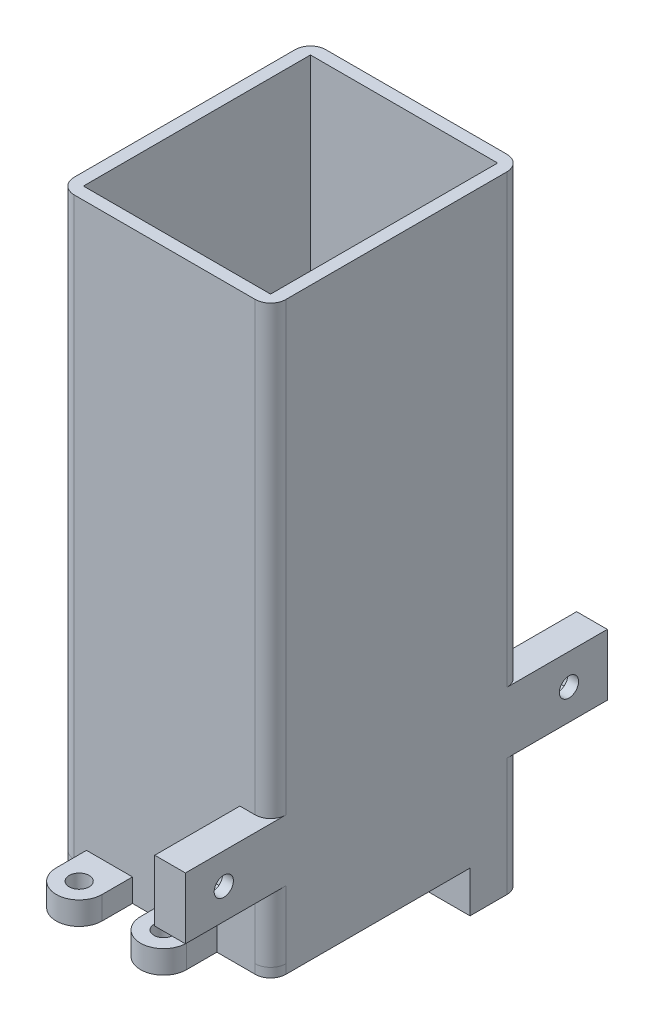
SolidWorks part; units mm, degrees
ref_plane "Front Plane" through (0, 0, 0) normal (0, 0, 1) x (1, 0, 0)
ref_plane "Top Plane" through (0, 0, 0) normal (0, 1, 0) x (1, 0, 0)
ref_plane "Right Plane" through (0, 0, 0) normal (1, 0, 0) x (0, 0, -1)
sketch "Sketch2" plane through (0, 0, 0) normal (0, 1, 0) x (1, 0, 0)
  line L5 (0, 0) -> (30.988, 0)
  line L6 (0, 0) -> (0, 37.592)
  line L7 (0, 37.592) -> (30.988, 37.592)
  line L8 (30.988, 0) -> (30.988, 37.592)
  line L9 (-2.032, 39.624) -> (33.02, 39.624)
  line L10 (-2.032, 39.624) -> (-2.032, -2.032)
  line L11 (-2.032, -2.032) -> (33.02, -2.032)
  line L12 (33.02, 39.624) -> (33.02, -2.032)
  dimension "D1" = 30.988
  dimension "D2" = 37.592
  dimension "D5" = 2.032
  dimension "D6" = 2.032
  dimension "D7" = 2.032
  dimension "D8" = 2.032
extrude "Boss-Extrude2" add sketch "Sketch2" along normal blind 101.6
sketch "Sketch3" plane through (0, 0, 0) normal (0, -1, 0) x (1, 0, 0)
  line L1 (33.02, 2.032) -> (-2.032, 2.032)
  line L2 (33.02, 2.032) -> (33.02, -39.624)
  line L3 (33.02, -39.624) -> (-2.032, -39.624)
  line L4 (-2.032, 2.032) -> (-2.032, -39.624)
extrude "Boss-Extrude3" add sketch "Sketch3" along normal blind 2.032
sketch "Sketch4" plane through (0, 0, 0) normal (0, 1, 0) x (1, 0, 0)
  line L0 (0, 0) -> (30.988, 0) construction
  line L2 (33.02, 39.624) -> (33.02, -2.032) construction
  circle A0 centre (16.51, 14.224) radius 12.7
  dimension "D1" = 25.4
  dimension "D2" = 14.224
  dimension "D3" = 16.51
extrude "Cut-Extrude1" cut sketch "Sketch4" against normal through all and the other way blind 29.21
sketch "Sketch6" plane through (0, 0, 0) normal (1, 0, 0) x (0, 0, -1)
  line L0 (37.592, 0) -> (31.242, 0)
  line L1 (37.592, 0) -> (0, 0) construction
  line L4 (31.242, 0) -> (31.242, 7.112)
  line L5 (31.242, 7.112) -> (37.592, 0)
  line L6 (39.624, 101.6) -> (39.624, -2.032) construction
  dimension "D1" = 6.35
  dimension "D2" = 7.112
  dimension "D3" = 2.032
extrude "Boss-Extrude4" add sketch "Sketch6" along normal blind 31.75
fillet "Fillet1" radius 0.254 1 edges at (15.494, 7.112, -31.242)
fillet "Fillet2" radius 2.54 4 edges at (-2.032, 49.784, -39.624) (33.02, 49.784, -39.624) (33.02, 49.784, 2.032) (-2.032, 49.784, 2.032)
fillet "Fillet3" radius 0.508 2 edges at (16.51, -2.032, -1.524) (16.51, 0, -1.524)
sketch "Sketch7" plane through (33.02, 0, 0) normal (1, 0, 0) x (0, 0, -1)
  line L1 (-2.032, -2.032) -> (27.178, -2.032)
  line L2 (-2.032, -2.032) -> (-2.032, 6.35)
  line L3 (-2.032, 6.35) -> (27.178, 6.35)
  line L4 (27.178, -2.032) -> (27.178, 6.35)
  dimension "D1" = 29.21
  dimension "D2" = 8.382
extrude "Cut-Extrude2" cut sketch "Sketch7" against normal through all
sketch "Sketch8" plane through (33.02, 0, 0) normal (1, 0, 0) x (0, 0, -1)
  line L0 (27.178, -2.032) -> (27.178, 6.35) construction
  line L1 (-2.032, 6.35) -> (27.178, 6.35)
  line L2 (-2.032, 6.35) -> (-2.032, 4.826)
  line L3 (-2.032, 4.826) -> (27.178, 4.826)
  line L4 (27.178, 6.35) -> (27.178, 4.826)
  dimension "D1" = 1.524
extrude "Boss-Extrude5" add sketch "Sketch8" against normal through all
fillet "Fillet6" radius 2.54 2 edges at (-2.032, 5.588, 2.032) (33.02, 5.588, 2.032)
sketch "Sketch9" plane through (0, 6.35, 0) normal (0, 1, 0) x (1, 0, 0)
  circle A0 centre (16.51, 14.224) radius 12.7 construction
  circle A1 centre (16.51, 14.224) radius 12.7
extrude "Cut-Extrude3" cut sketch "Sketch9" against normal through all
fillet "Fillet7" radius 0.508 2 edges at (16.51, 4.826, -26.924) (16.51, 6.35, -1.524)
sketch "Sketch11" plane through (0, 0, -31.242) normal (0, 0, 1) x (1, 0, 0)
  line L9 (-2.032, -2.032) -> (30.226, -2.032)
  line L15 (-2.032, -2.032) -> (-2.032, 6.35)
  line L19 (-2.032, 6.35) -> (33.02, 6.35)
  line L20 (33.02, 6.35) -> (33.02, -2.032)
  line L21 (33.02, -2.032) -> (30.226, -2.032)
extrude "Boss-Extrude6" add sketch "Sketch11" along normal blind 4.064
sketch "Sketch12" plane through (-2.032, 0, 0) normal (-1, 0, 0) x (0, 0, 1)
  line L1 (-27.178, -2.032) -> (-30.988, -2.032)
  line L2 (-27.178, -2.032) -> (-27.178, 2.286)
  line L3 (-27.178, 2.286) -> (-30.988, 2.286)
  line L4 (-30.988, -2.032) -> (-30.988, 2.286)
  dimension "D1" = 3.81
extrude "Cut-Extrude4" cut sketch "Sketch12" against normal through all
sketch "Sketch14" plane through (33.02, 0, 0) normal (1, 0, 0) x (0, 0, -1)
  line L0 (18.796, 101.6) -> (18.796, 75.8817) construction
  line L1 (0.508, 101.6) -> (37.084, 101.6) construction
  line L2 (0.508, 4.826) -> (27.178, 4.826) construction
  line L3 (-16.129, 27.686) -> (53.721, 27.686)
  line L4 (-16.129, 27.686) -> (-16.129, 17.526)
  line L5 (-16.129, 17.526) -> (53.721, 17.526)
  line L6 (53.721, 27.686) -> (53.721, 17.526)
  line L7 (-16.129, 27.686) -> (53.721, 17.526) construction
  line L8 (-16.129, 17.526) -> (53.721, 27.686) construction
  point P4 (18.796, 22.606)
  dimension "D1" = 12.7
  dimension "D2" = 69.85
  dimension "D3" = 10.16
extrude "Boss-Extrude7" add sketch "Sketch14" against normal blind 5.08
sketch "Sketch16" plane through (0, 101.6, 0) normal (0, 1, 0) x (1, 0, 0)
  line L1 (30.988, 0) -> (0, 0)
  line L2 (30.988, 0) -> (30.988, 37.592)
  line L3 (30.988, 37.592) -> (0, 37.592)
  line L4 (0, 0) -> (0, 37.592)
extrude "Cut-Extrude5" cut sketch "Sketch16" against normal blind 93.98
sketch "Sketch17" plane through (33.02, 0, 0) normal (1, 0, 0) x (0, 0, -1)
  line L0 (53.721, 17.526) -> (53.721, 27.686) construction
  line L1 (-16.129, 27.686) -> (-16.129, 17.526) construction
  line L2 (0.508, 27.686) -> (-16.129, 27.686) construction
  line L3 (53.721, 27.686) -> (37.084, 27.686) construction
  circle A0 centre (-9.779, 22.606) radius 1.5875
  circle A1 centre (47.371, 22.606) radius 1.5875
  dimension "D1" = 3.175
  dimension "D2" = 3.175
  dimension "D3" = 6.35
  dimension "D4" = 6.35
  dimension "D5" = 5.08
  dimension "D6" = 5.08
extrude "Cut-Extrude6" cut sketch "Sketch17" against normal through all
sketch "Sketch18" plane through (27.94, 0, 0) normal (-1, 0, 0) x (0, 0, 1)
  line L1 (-46.3935, 19.719) -> (-44.382, 22.0091)
  line L2 (-44.382, 22.0091) -> (-45.3596, 24.8961)
  line L3 (-45.3596, 24.8961) -> (-48.3485, 25.493)
  line L4 (-48.3485, 25.493) -> (-50.36, 23.2029)
  line L5 (-50.36, 23.2029) -> (-49.3824, 20.3159)
  line L6 (-49.3824, 20.3159) -> (-46.3935, 19.719)
  line L7 (10.7565, 19.719) -> (12.768, 22.0091)
  line L8 (12.768, 22.0091) -> (11.7904, 24.8961)
  line L9 (11.7904, 24.8961) -> (8.8015, 25.493)
  line L10 (8.8015, 25.493) -> (6.79, 23.2029)
  line L11 (6.79, 23.2029) -> (7.7676, 20.3159)
  line L12 (7.7676, 20.3159) -> (10.7565, 19.719)
  circle A0 centre (-47.371, 22.606) radius 2.6396 construction
  circle A1 centre (9.779, 22.606) radius 2.6396 construction
  dimension "D1" = 6.096
  dimension "D2" = 6.096
extrude "Cut-Extrude7" cut sketch "Sketch18" against normal blind 3.302
sketch "Sketch19" plane through (0, 4.826, 0) normal (0, -1, 0) x (1, 0, 0)
  line L0 (24.13, 2.032) -> (24.13, 7.0514)
  line L1 (0.508, 2.032) -> (30.48, 2.032) construction
  line L3 (16.51, 7.0514) -> (16.51, 2.032)
  line L5 (10.16, 2.032) -> (10.16, 7.0514)
  line L7 (2.54, 7.0514) -> (2.54, 2.032)
  line L8 (2.54, 2.032) -> (10.16, 2.032)
  line L9 (16.51, 2.032) -> (24.13, 2.032)
  line L10 (27.94, 2.032) -> (27.94, 16.129) construction
  line L11 (0, -31.242) -> (0, 0) construction
  arc A0 (24.13, 7.0514) -> (16.51, 7.0514) centre (20.32, 7.0514) ccw
  arc A1 (10.16, 7.0514) -> (2.54, 7.0514) centre (6.35, 7.0514) ccw
  circle A2 centre (20.32, 7.0514) radius 1.5875
  circle A3 centre (6.35, 7.0514) radius 1.651
  dimension "D4" = 3.175
  dimension "D5" = 3.302
  dimension "D1" = 6.35
  dimension "D2" = 7.62
  dimension "D3" = 7.62
  dimension "D6" = 3.81
  dimension "D7" = 2.54
extrude "Boss-Extrude10" add sketch "Sketch19" against normal blind 3.81 separate body
sketch "Sketch20" plane through (0, -2.032, 0) normal (0, -1, 0) x (1, 0, 0)
  line L0 (0.508, -39.624) -> (30.48, -39.624) construction
  line L13 (1.778, -39.624) -> (9.398, -39.624)
  line L14 (1.778, -44.6434) -> (1.778, -39.624)
  line L15 (15.748, -39.624) -> (23.368, -39.624)
  line L16 (23.368, -39.624) -> (23.368, -44.6434)
  line L17 (15.748, -44.6434) -> (15.748, -39.624)
  line L18 (9.398, -39.624) -> (9.398, -44.6434)
  arc A8 (9.398, -44.6434) -> (1.778, -44.6434) centre (5.588, -44.6434) cw
  arc A9 (23.368, -44.6434) -> (15.748, -44.6434) centre (19.558, -44.6434) cw
  circle A10 centre (19.558, -44.6434) radius 1.5875
  circle A11 centre (5.588, -44.6434) radius 1.651
  dimension "D1" = 5.0194
  dimension "D4" = 5.0194
  dimension "D6" = 3.81
  dimension "D7" = 3.81
  dimension "D2" = 7.62
  dimension "D3" = 5.0194
  dimension "D5" = 5.0194
  dimension "D8" = 0
  dimension "D9" = 0
extrude "Boss-Extrude11" add sketch "Sketch20" against normal blind 2.54
sketch "Sketch21" plane through (33.02, 0, 0) normal (1, 0, 0) x (0, 0, -1)
  line L1 (27.178, 2.286) -> (30.988, 2.286)
  line L2 (27.178, 2.286) -> (27.178, 4.826)
  line L3 (27.178, 4.826) -> (30.988, 4.826)
  line L4 (30.988, 2.286) -> (30.988, 4.826)
extrude "Cut-Extrude8" cut sketch "Sketch21" against normal through all
